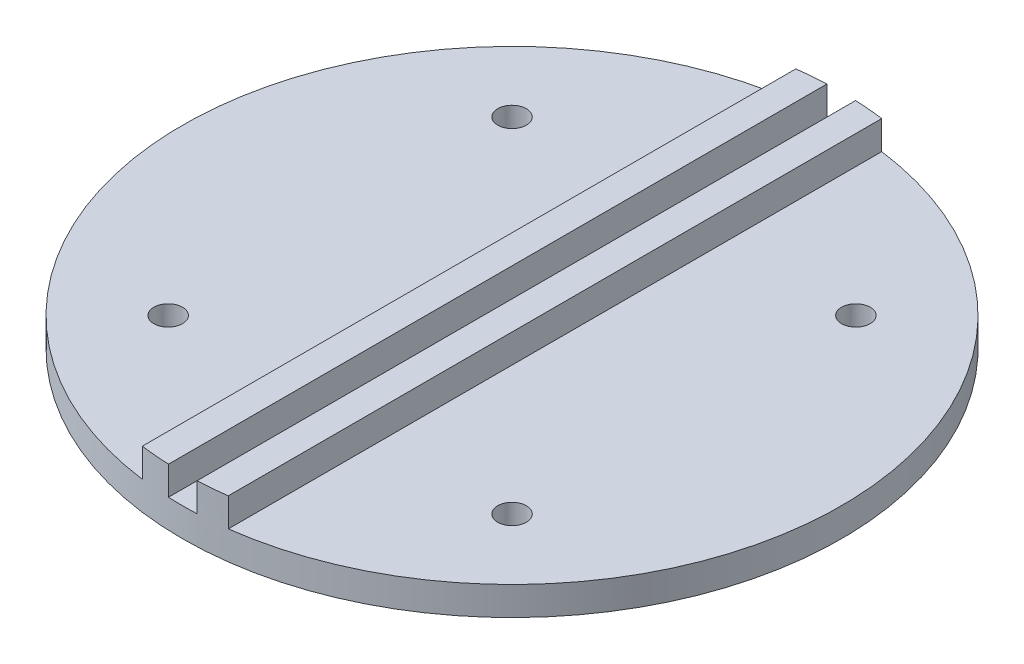
SolidWorks part; units mm, degrees
material "ABS PC"
ref_plane "Front Plane" through (0, 0, 0) normal (0, 0, 1) x (1, 0, 0)
ref_plane "Top Plane" through (0, 0, 0) normal (0, 1, 0) x (1, 0, 0)
ref_plane "Right Plane" through (0, 0, 0) normal (1, 0, 0) x (0, 0, -1)
sketch "Sketch5" plane through (0, 0, 0) normal (0, 1, 0) x (1, 0, 0)
  circle A0 centre (0, 0) radius 73.025
  circle A1 centre (38.1, 38.1) radius 3.175
  circle A2 centre (38.1, -38.1) radius 3.175
  circle A3 centre (-38.1, 38.1) radius 3.175
  circle A4 centre (-38.1, -38.1) radius 3.175
extrude "Boss-Extrude1" add sketch "Sketch5" along normal blind 6.35
sketch "Sketch6" plane through (0, 6.35, 0) normal (0, 1, 0) x (1, 0, 0)
  line L1 (3.175, 0) -> (3.175, 72.9559)
  line L3 (3.175, 0) -> (3.175, -72.9559)
  line L4 (0, 0) -> (3.175, 0)
  line L5 (-3.175, 0) -> (-3.175, 72.9559)
  line L6 (-9.525, 0) -> (-9.525, 72.4011)
  line L7 (-9.525, 0) -> (-9.525, -72.4011)
  line L8 (-3.175, 0) -> (-3.175, -72.9559)
  line L9 (9.525, 0) -> (9.525, 72.4011)
  line L10 (9.525, 0) -> (9.525, -72.4011)
  circle A0 centre (0, 0) radius 73.025 construction
  circle M4 centre (0, 0) radius 73.025
extrude "Boss-Extrude3" add sketch "Sketch6" along normal blind 6.35 contours L8 L5 L6 L7 M4 | L10 L9 L1 L3 M4 region at (6.346, 6.35, 0) region at (-6.346, 6.35, 0)
